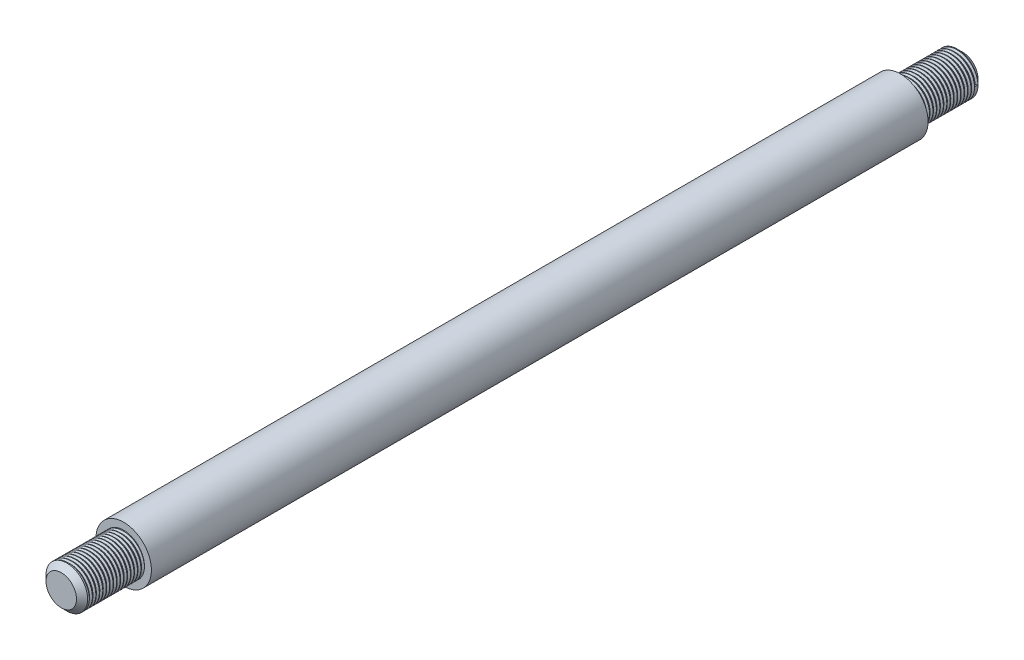
SolidWorks part; units mm, degrees
material "Chrome Stainless Steel"
ref_plane "Front Plane" through (0, 0, 0) normal (0, 0, 1) x (1, 0, 0)
ref_plane "Top Plane" through (0, 0, 0) normal (0, 1, 0) x (1, 0, 0)
ref_plane "Right Plane" through (0, 0, 0) normal (1, 0, 0) x (0, 0, -1)
sketch "Sketch1" plane through (0, 0, 0) normal (0, 0, 1) x (1, 0, 0)
  circle A0 centre (0, 0) radius 2
  dimension "D1" = 4
extrude "Boss-Extrude1" add sketch "Sketch1" against normal blind 56
sketch "Sketch2" plane through (0, 0, 0) normal (0, 0, 1) x (1, 0, 0)
  circle A0 centre (0, 0) radius 1.5
  dimension "D1" = 3
extrude "Boss-Extrude2" add sketch "Sketch2" along normal blind 4.5
sketch "Sketch3" plane through (0, 0, -56) normal (0, 0, -1) x (-1, 0, 0)
  circle A0 centre (0, 0) radius 1.5
  circle A1 centre (0, 0) radius 1.5 construction
extrude "Boss-Extrude3" add sketch "Sketch3" along normal blind 4.5
chamfer "Chamfer1" distance 0.4 angle 45 2 edges at (1.5, 0, 4.5) (-1.5, 0, -60.5)
thread "Thread1" pitch 0.25 method cut profile "Thread Profile1" start angle 0, offset 0, length 4, pitch 0.25, diameter 3
ref_plane "Plane1" through (-1.5, 0, 4.1) normal (0, -1, 0) x (-1, 0, 0)
sketch "Thread Profile1" plane through (-1.5, 0, 4.1) normal (0, -1, 0) x (-1, 0, 0)
  line L0 (0, 0) -> (0, 0.25) construction
  line L11 (0, 0) -> (0, 0.2187)
  line L12 (0, 0.2187) -> (-0.1353, 0.1406)
  line L13 (-0.1353, 0.1406) -> (-0.1353, 0.0781)
  line L15 (-0.1353, 0.0781) -> (0, 0)
  line L17 (-0.1353, 0.1094) -> (0, 0.1094) construction
  point P2 (0, 0)
  dimension "Pitch" = 0.25
  dimension "Profile_Angle" = 60
  dimension "Profile_Land" = 0.0625
  dimension "Profile_Height" = 0.1353
thread "Thread2" pitch 0.25 method cut profile "Thread Profile2" start angle 0, offset 0, length 4, pitch 0.25, diameter 3
ref_plane "Plane2" through (1.5, 0, -60.1) normal (0, -1, 0) x (1, 0, 0)
sketch "Thread Profile2" plane through (1.5, 0, -60.1) normal (0, -1, 0) x (1, 0, 0)
  line L0 (0, 0) -> (0, 0.25) construction
  line L11 (0, 0) -> (0, 0.2187)
  line L12 (0, 0.2187) -> (-0.1353, 0.1406)
  line L13 (-0.1353, 0.1406) -> (-0.1353, 0.0781)
  line L15 (-0.1353, 0.0781) -> (0, 0)
  line L17 (-0.1353, 0.1094) -> (0, 0.1094) construction
  point P2 (0, 0)
  dimension "Pitch" = 0.25
  dimension "Profile_Angle" = 60
  dimension "Profile_Land" = 0.0625
  dimension "Profile_Height" = 0.1353
